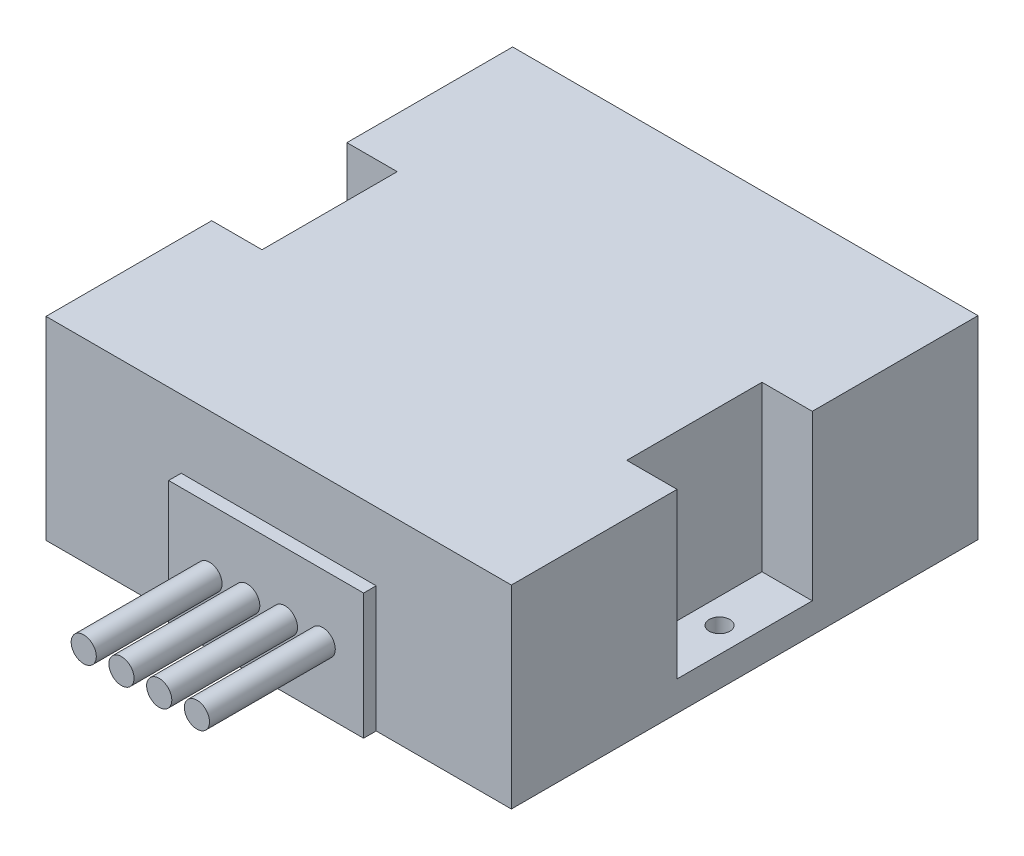
SolidWorks part; units mm, degrees
ref_plane "Front Plane" through (0, 0, 0) normal (0, 0, 1) x (1, 0, 0)
ref_plane "Top Plane" through (0, 0, 0) normal (0, 1, 0) x (1, 0, 0)
ref_plane "Right Plane" through (0, 0, 0) normal (1, 0, 0) x (0, 0, -1)
sketch "Sketch1" plane through (0, 0, 0) normal (0, 1, 0) x (1, 0, 0)
  line L1 (-37, 37.1) -> (37, 37.1)
  line L2 (-37, 37.1) -> (-37, -37.1)
  line L3 (-37, -37.1) -> (37, -37.1)
  line L4 (37, 37.1) -> (37, -37.1)
  line L5 (-37, 37.1) -> (37, -37.1) construction
  line L6 (-37, -37.1) -> (37, 37.1) construction
  point P0 (0, 0)
  dimension "D1" = 74
  dimension "D2" = 74.2
extrude "Boss-Extrude1" add sketch "Sketch1" along normal mid plane 30.85
sketch "Sketch3" plane through (0, 15.425, 0) normal (0, 1, 0) x (1, 0, 0)
  line L0 (-37, 37.1) -> (-37, -37.1) construction
  line L1 (-29, -10.75) -> (-37, -10.75)
  line L2 (-29, -10.75) -> (-29, 10.75)
  line L3 (-29, 10.75) -> (-37, 10.75)
  line L4 (-37, -10.75) -> (-37, 10.75)
  line L5 (-29, -10.75) -> (-37, 10.75) construction
  line L6 (-29, 10.75) -> (-37, -10.75) construction
  point P0 (-33, 0)
  dimension "D1" = 8
  dimension "D2" = 21.5
extrude "Cut-Extrude1" cut sketch "Sketch3" against normal blind 26.1
hole_wizard "#30 (0.1285) Diameter Hole1" positions "Sketch4" profile "Sketch5" hole size "#30" standard "ANSI Inch" end condition through all
sketch "Sketch4" plane through (0, -10.675, 0) normal (0, 1, 0) x (1, 0, 0)
  line L0 (-29, 10.75) -> (-37, 10.75) construction
  point P0 (-33, 0)
  point P5 (-33, 10.75)
sketch "Sketch5" plane through (-33, -10.675, 0) normal (1, 0, 0) x (0, 0, 1)
  line L0 (0, 0) -> (0, 4.75)
  line L1 (0, 4.75) -> (1.6319, 4.75)
  line L2 (1.6319, 4.75) -> (1.6319, 0)
  line L5 (1.6319, 0) -> (0, 0)
  line L11 (0, -6.35) -> (0, 107.95) construction
  dimension "Thru Hole Dia." = 3.2639
  dimension "Thru Hole Depth" = 4.75
sketch "Sketch6" plane through (0, 0, 37.1) normal (0, 0, 1) x (1, 0, 0)
  line L0 (-37, -15.425) -> (37, -15.425) construction
  line L1 (-15.5, 4.575) -> (15.5, 4.575)
  line L2 (-15.5, 4.575) -> (-15.5, -15.425)
  line L3 (-15.5, -15.425) -> (15.5, -15.425)
  line L4 (15.5, 4.575) -> (15.5, -15.425)
  line L5 (-15.5, 4.575) -> (15.5, -15.425) construction
  line L6 (-15.5, -15.425) -> (15.5, 4.575) construction
  point P0 (0, -5.425)
  dimension "D1" = 20
  dimension "D2" = 31
extrude "Boss-Extrude2" add sketch "Sketch6" along normal blind 2
sketch "Sketch7" plane through (0, 0, 39.1) normal (0, 0, 1) x (1, 0, 0)
  line L2 (-15.5, 4.575) -> (-15.5, -15.425) construction
  circle A0 centre (-9, -5.425) radius 2
  circle A1 centre (-3, -5.425) radius 2
  point P13 (-15.5, -5.425)
  dimension "D1" = 4
  dimension "D2" = 3
  dimension "D3" = 6
extrude "Boss-Extrude3" add sketch "Sketch7" along normal blind 20
mirror "Mirror1" about plane through (0, 0, 0) normal (1, 0, 0) of "Boss-Extrude3", "#30 (0.1285) Diameter Hole1", "Cut-Extrude1"
